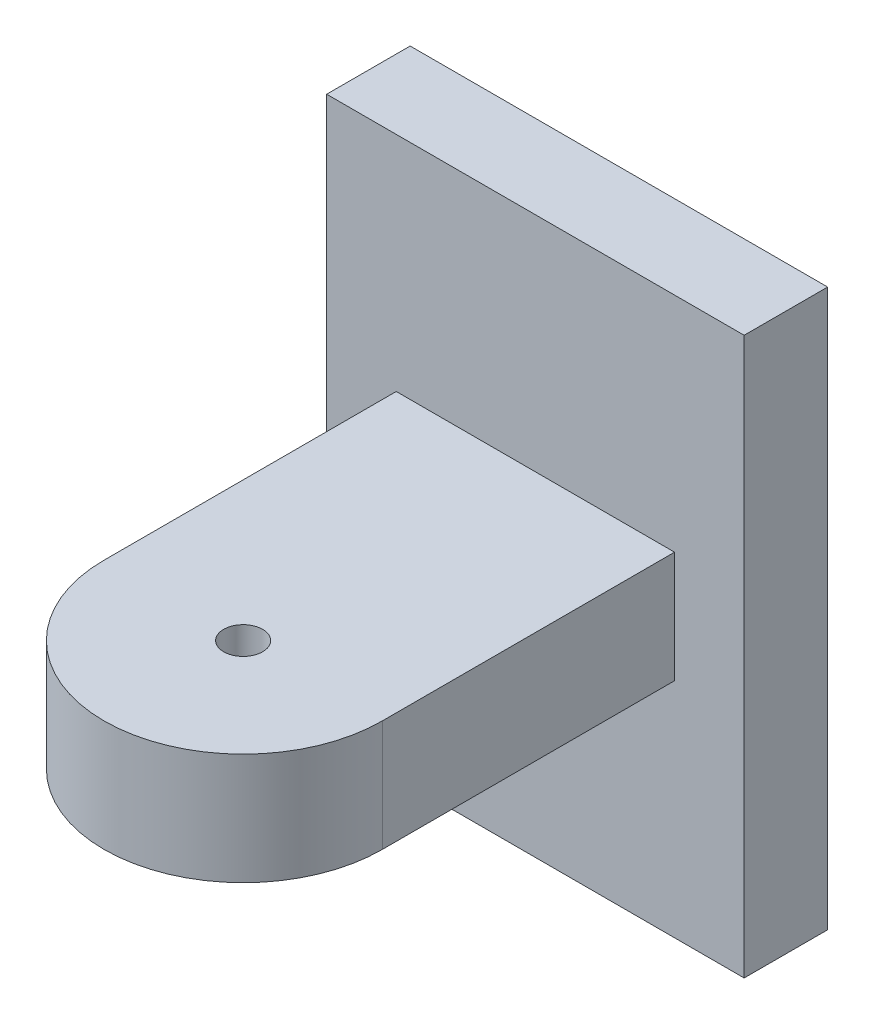
SolidWorks part; units mm, degrees
material "PVC 0.007 Plasticized"
ref_plane "Ön Düzlem" through (0, 0, 0) normal (0, 0, 1) x (1, 0, 0)
ref_plane "Üst Düzlem" through (0, 0, 0) normal (0, 1, 0) x (1, 0, 0)
ref_plane "Sağ Düzlem" through (0, 0, 0) normal (1, 0, 0) x (0, 0, -1)
sketch "Sketch1" plane through (0, 0, 0) normal (0, 0, 1) x (1, 0, 0)
  line L1 (7.5, 10) -> (-7.5, 10)
  line L2 (7.5, 10) -> (7.5, -10)
  line L3 (7.5, -10) -> (-7.5, -10)
  line L4 (-7.5, 10) -> (-7.5, -10)
  line L5 (7.5, 10) -> (-7.5, -10) construction
  line L6 (7.5, -10) -> (-7.5, 10) construction
  point P0 (0, 0)
  dimension "D1" = 15
  dimension "D2" = 20
extrude "Boss-Extrude1" add sketch "Sketch1" along normal blind 3
sketch "Sketch2" plane through (0, 10, 0) normal (0, 1, 0) x (1, 0, 0)
  line L0 (-5, -3) -> (-5, -13.5)
  line L1 (-5, -3) -> (5, -3)
  line L2 (5, -3) -> (5, -13.5)
  line L3 (7.5, -3) -> (-7.5, -3) construction
  arc A0 (-5, -13.5) -> (5, -13.5) centre (0, -13.5) ccw
  circle A1 centre (0, -13.5) radius 0.7
  point P6 (0, -3)
  point P7 (0, -3)
  point P9 (0, -18.5)
  dimension "D3" = 1.4
  dimension "D1" = 10
  dimension "D2" = 15.5
extrude "Boss-Extrude2" add sketch "Sketch2" against normal blind 14
extrude "Cut-Extrude1" cut sketch "Sketch2<2>" against normal blind 6
sketch "Sketch2<2>" plane through (0, 10, 0) normal (0, 1, 0) x (1, 0, 0) same geometry as "Sketch2"
sketch "Sketch3" plane through (0, -4, 0) normal (0, -1, 0) x (1, 0, 0)
  line L0 (5, 13.5) -> (5, 3)
  line L1 (5, 3) -> (-5, 3)
  line L2 (-5, 3) -> (-5, 13.5)
  arc A0 (5, 13.5) -> (-5, 13.5) centre (0, 13.5) ccw
extrude "Cut-Extrude2" cut sketch "Sketch3" against normal blind 2
sketch "Sketch4" plane through (0, 4, 0) normal (0, 1, 0) x (1, 0, 0)
  line L0 (-5, -13.5) -> (-5, -3)
  line L1 (-5, -3) -> (5, -3)
  line L2 (5, -3) -> (5, -13.5)
  arc A0 (-5, -13.5) -> (5, -13.5) centre (0, -13.5) ccw
extrude "Cut-Extrude3" cut sketch "Sketch4" against normal blind 2
